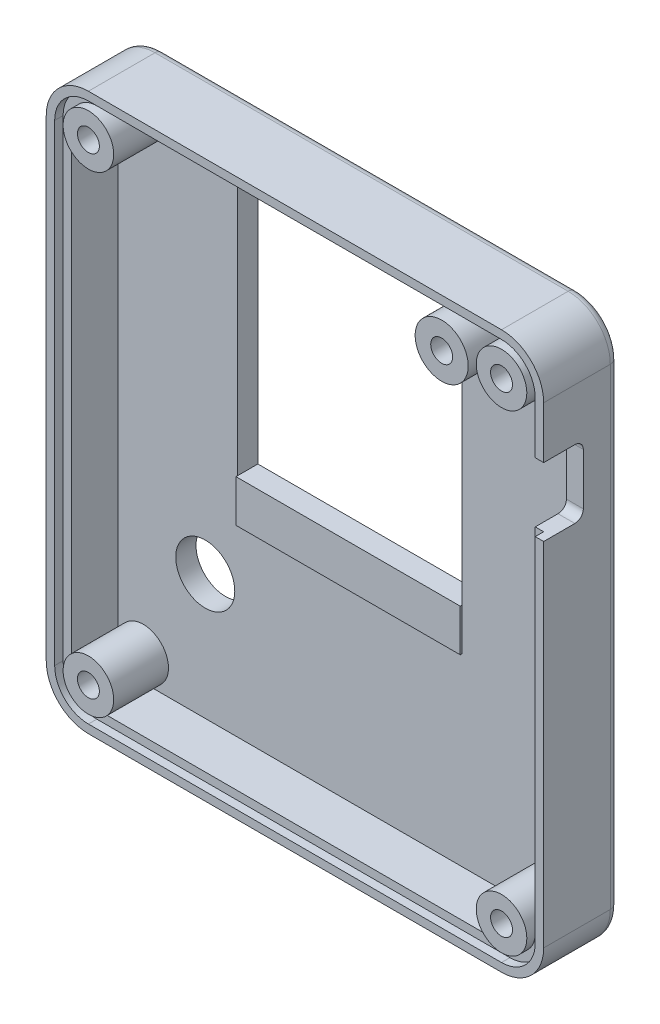
SolidWorks part; units mm, degrees
ref_plane "Спереди" through (0, 0, 0) normal (0, 0, 1) x (1, 0, 0)
ref_plane "Сверху" through (0, 0, 0) normal (0, 1, 0) x (1, 0, 0)
ref_plane "Справа" through (0, 0, 0) normal (1, 0, 0) x (0, 0, -1)
sketch "Эскиз1" plane through (0, 0, 0) normal (0, 0, 1) x (1, 0, 0)
  line L0 (29.5, 0) -> (29.5, -66) construction
  line L1 (0, 0) -> (59, 0)
  line L2 (0, 0) -> (0, -66)
  line L3 (0, -66) -> (59, -66)
  line L4 (59, 0) -> (59, -66)
  line L9 (29.5, -10) -> (29.5, -52.4) construction
  circle A1 centre (12.36, -49.17) radius 3.5
  dimension "D8" = 7
  dimension "D1" = 59
  dimension "D2" = 49.17
  dimension "D3" = 66
  dimension "D4" = 12.36
extrude "Бобышка-Вытянуть1" add sketch "Эскиз1" along normal blind 2.4
sketch "Эскиз4" plane through (0, 0, 2.4) normal (0, 0, 1) x (1, 0, 0)
  line L19 (0, 0) -> (59, 0)
  line L20 (0, 0) -> (0, -66)
  line L21 (0, -66) -> (59, -66)
  line L22 (59, 0) -> (59, -66)
  line L23 (5.1, -2) -> (53.9, -2)
  line L24 (2, -5.1) -> (2, -60.9)
  line L25 (5.1, -64) -> (53.9, -64)
  line L26 (57, -5.1) -> (57, -60.9)
  arc A0 (2, -60.9) -> (5.1, -64) centre (5.1, -60.9) ccw
  arc A1 (53.9, -64) -> (57, -60.9) centre (53.9, -60.9) ccw
  arc A2 (53.9, -2) -> (57, -5.1) centre (53.9, -5.1) cw
  arc A3 (5.1, -2) -> (2, -5.1) centre (5.1, -5.1) ccw
  dimension "D5" = 3.1
  dimension "D1" = 2
  dimension "D2" = 2
  dimension "D3" = 2
  dimension "D4" = 2
extrude "Бобышка-Вытянуть6" add sketch "Эскиз4" along normal blind 5.5
fillet "Скругление1" radius 5 1 edges at (0, 0, 3.95)
fillet "Скругление2" radius 5 3 edges at (0, -66, 3.95) (59, -66, 3.95) (59, 0, 3.95)
sketch "Эскиз14" plane through (0, 0, 2.4) normal (0, 0, 1) x (1, 0, 0)
  line L0 (0, -5) -> (0, -61) construction
  line L1 (59, -61) -> (59, -5) construction
  line L2 (5, -66) -> (54, -66) construction
  line L3 (5, -66) -> (54, -66) construction
  line L4 (54, 0) -> (5, 0) construction
  circle A0 centre (5, -5) radius 3
  circle A1 centre (5, -61) radius 3
  circle A2 centre (54, -61) radius 3
  circle A3 centre (54, -5) radius 3
  circle A4 centre (5, -5) radius 1.3
  circle A5 centre (54, -5) radius 1.3
  circle A6 centre (5, -61) radius 1.3
  circle A7 centre (54, -61) radius 1.3
  dimension "D1" = 5
  dimension "D2" = 5
  dimension "D3" = 5
  dimension "D4" = 5
  dimension "D5" = 5
  dimension "D6" = 5
  dimension "D7" = 5
  dimension "D8" = 5
  dimension "D9" = 2.6
  dimension "D10" = 6
  dimension "D11" = 2.6
extrude "Бобышка-Вытянуть7" add sketch "Эскиз14" along normal blind 6.5
sketch "Эскиз15" plane through (0, 0, 7.9) normal (0, 0, 1) x (1, 0, 0)
  line L0 (5, -66) -> (54, -66) construction
  line L5 (5, 0) -> (54, 0)
  line L6 (0, -5) -> (0, -61)
  line L7 (5, -66) -> (54, -66)
  line L8 (59, -5) -> (59, -61)
  line L9 (59, -61) -> (59, -5) construction
  line L10 (5, -1) -> (54, -1)
  line L11 (1, -5) -> (1, -61)
  line L12 (5, -65) -> (54, -65)
  line L13 (58, -5) -> (58, -61)
  arc A0 (0, -61) -> (5, -66) centre (5, -61) ccw
  arc A1 (54, -66) -> (59, -61) centre (54, -61) ccw
  arc A2 (54, 0) -> (59, -5) centre (54, -5) cw
  arc A3 (5, 0) -> (0, -5) centre (5, -5) ccw
  arc A4 (5, -1) -> (1, -5) centre (5, -5) ccw
  arc A5 (54, -1) -> (58, -5) centre (54, -5) cw
  arc A6 (54, -65) -> (58, -61) centre (54, -61) ccw
  arc A7 (1, -61) -> (5, -65) centre (5, -61) ccw
  point P23 (0, 0)
  dimension "D5" = 5
  dimension "D6" = 4
  dimension "D1" = 1
  dimension "D2" = 1
  dimension "D3" = 1
  dimension "D4" = 1
extrude "Бобышка-Вытянуть10" add sketch "Эскиз15" along normal blind 1 separate body
fillet "Скругление3" radius 1 8 edges at (57.5355, -1.4645, 0) (59, -33, 0) (57.5355, -64.5355, 0) (29.5, -66, 0) (1.4645, -64.5355, 0) (0, -33, 0) (1.4645, -1.4645, 0) (29.5, 0, 0)
sketch "Эскиз20" plane through (59, 0, 0) normal (1, 0, 0) x (0, 0, -1)
  line L0 (-8.9, -61) -> (-8.9, -5) construction
  line L1 (-8.9, -11.15) -> (-5.2, -11.15)
  line L2 (-8.9, -11.15) -> (-8.9, -19.25)
  line L3 (-8.9, -19.25) -> (-5.2, -19.25)
  line L4 (-4.2, -12.15) -> (-4.2, -18.25)
  line L5 (-7.9, 0) -> (-1, 0) construction
  arc A0 (-5.2, -19.25) -> (-4.2, -18.25) centre (-5.2, -18.25) ccw
  arc A1 (-5.2, -11.15) -> (-4.2, -12.15) centre (-5.2, -12.15) cw
  point P10 (-4.2, -19.25)
  point P13 (-4.2, -11.15)
  dimension "D4" = 1
  dimension "D1" = 8.1
  dimension "D2" = 4.7
  dimension "D3" = 11.15
extrude "Вырез-Вытянуть1" cut sketch "Эскиз20" against normal blind 10
sketch "Эскиз23" plane through (0, 0, 0) normal (0, 0, -1) x (-1, 0, 0)
  line L1 (-16.2, -7.241) -> (-42.8, -7.241)
  line L2 (-16.2, -7.241) -> (-16.2, -37.141)
  line L3 (-16.2, -37.141) -> (-42.8, -37.141)
  line L4 (-42.8, -7.241) -> (-42.8, -37.141)
  dimension "D1" = 29.9
  dimension "D2" = 26.6
extrude "Вырез-Вытянуть4" cut sketch "Эскиз23" against normal blind 52
ref_axis "Ось1" through (29.5, -1, 0) along (0, -1, 0)
sketch "Эскиз24" plane through (0, 0, 2.4) normal (0, 0, 1) x (1, 0, 0)
  line L0 (42.8, -7.241) -> (16.2, -7.241)
  line L1 (42.8, -7.241) -> (42.8, -2.241)
  line L2 (16.2, -7.241) -> (16.2, -2.241)
  line L3 (42.8, -2.241) -> (16.2, -2.241)
  dimension "D1" = 5
extrude "Бобышка-Вытянуть11" add sketch "Эскиз24" along normal blind 0.2
sketch "Эскиз25" plane through (0, 0, 2.4) normal (0, 0, 1) x (1, 0, 0)
  line L0 (16.2, -37.141) -> (42.8, -37.141)
  line L1 (16.2, -37.141) -> (16.2, -42.141)
  line L2 (42.8, -37.141) -> (42.8, -42.141)
  line L3 (16.2, -42.141) -> (42.8, -42.141)
  line L4 (16.2, -37.141) -> (42.8, -37.141) construction
  dimension "D1" = 5
extrude "Бобышка-Вытянуть12" add sketch "Эскиз25" along normal blind 0.2 contours L3 L2 L0 L1
sketch "Эскиз26" plane through (0, 0, 2.4) normal (0, 0, 1) x (1, 0, 0)
  circle A0 centre (46.9, -5.7) radius 1.3
  circle A1 centre (54, -5) radius 1.3 construction
  arc A3 (53.9504, -2.0004) -> (56.9996, -5.0496) centre (54, -5) ccw construction
  circle A4 centre (54, -5) radius 1.3 construction
  circle A5 centre (46.9, -5.7) radius 3.1474
  dimension "D1" = 2.6
  dimension "D3" = 0.7
  dimension "D4" = 7.1
  dimension "D2" = 3
extrude "Бобышка-Вытянуть13" add sketch "Эскиз26" along normal blind 6.5
sketch "Эскиз27" plane through (0, 0, 0) normal (0, 0, -1) x (-1, 0, 0)
  line L0 (-59, -61) -> (-59, -5) construction
  line L1 (-5, -66) -> (-54, -66) construction
  circle A0 centre (-44.3, -54.4) radius 4
  dimension "D1" = 14.7
  dimension "D3" = 8
  dimension "D2" = 11.6
extrude "Вырез-Вытянуть5" cut sketch "Эскиз27" against normal blind 0.4 contours A0
sketch "Эскиз28" plane through (0, 0, 0.4) normal (0, 0, -1) x (-1, 0, 0)
  circle A1 centre (-44.3, -54.4) radius 3.1752
extrude "Бобышка-Вытянуть14" add sketch "Эскиз28" along normal blind 0.4 contours A1
fillet "Скругление4" radius 0.5 1 edges at (40.3, -54.4, 0)
fillet "Скругление5" radius 0.5 1 edges at (41.1248, -54.4, 0)
